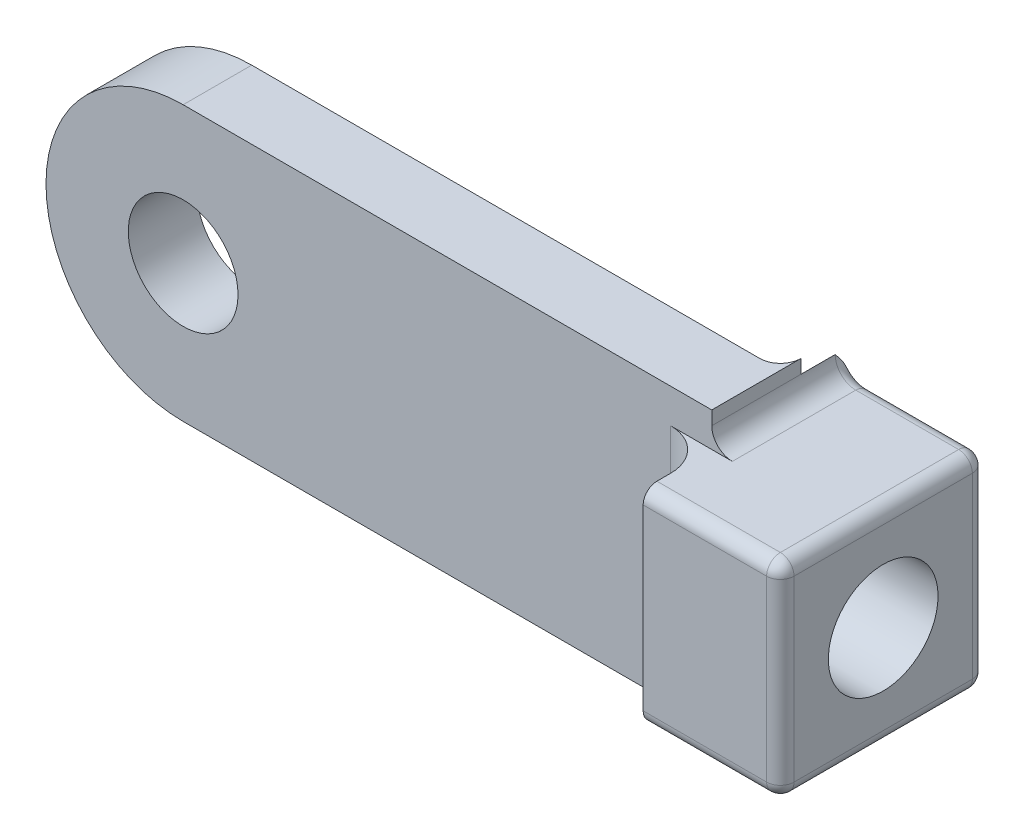
SolidWorks part; units mm, degrees
ref_plane "Front Plane" through (0, 0, 0) normal (0, 0, 1) x (1, 0, 0)
ref_plane "Top Plane" through (0, 0, 0) normal (0, 1, 0) x (1, 0, 0)
ref_plane "Right Plane" through (0, 0, 0) normal (1, 0, 0) x (0, 0, -1)
sketch "Sketch1" plane through (0, 0, 0) normal (0, 0, 1) x (1, 0, 0)
  line L0 (-22.5, 0) -> (22.5, 0) construction
  line L1 (-22.5, 10) -> (22.5, 10)
  line L2 (-22.5, -10) -> (22.5, -10)
  arc A0 (-22.5, 10) -> (-22.5, -10) centre (-22.5, 0) ccw
  arc A1 (22.5, -10) -> (22.5, 10) centre (22.5, 0) ccw
  circle A2 centre (-22.5, 0) radius 4
  circle A3 centre (22.5, 0) radius 4
  point P2 (0, 0)
  dimension "D3" = 8
  dimension "D4" = 8
  dimension "D1" = 20
  dimension "D2" = 45
extrude "Boss-Extrude1" add sketch "Sketch1" along normal blind 5
sketch "Sketch2" plane through (0, 0, 5) normal (0, 0, 1) x (1, 0, 0)
  line L0 (22.5, 10) -> (-22.5, 10) construction
  line L1 (16.0416, 10) -> (41.2048, 10)
  line L2 (16.0416, 10) -> (16.0416, -10)
  line L3 (16.0416, -10) -> (41.2048, -10)
  line L4 (41.2048, 10) -> (41.2048, -10)
  line L5 (-22.5, -10) -> (22.5, -10) construction
extrude "Cut-Extrude1" cut sketch "Sketch2" against normal through all
sketch "Sketch3" plane through (16.0416, 0, 0) normal (1, 0, 0) x (0, 0, -1)
  line L1 (5, -7.5) -> (-10, -7.5)
  line L2 (5, -7.5) -> (5, 7.5)
  line L3 (5, 7.5) -> (-10, 7.5)
  line L4 (-10, -7.5) -> (-10, 7.5)
  line L6 (0, 10) -> (-5, 10) construction
  line L7 (-5, 10) -> (-5, -10) construction
  line L8 (0, 10) -> (0, -10) construction
  point P6 (5, 0)
  dimension "D1" = 10
  dimension "D2" = 5
  dimension "D3" = 5
  dimension "D4" = 15
extrude "Boss-Extrude2" add sketch "Sketch3" along normal blind 10
fillet "Fillet1" radius 1.5 3 edges at (16.0416, 7.5, 2.5) (16.0416, -7.5, 2.5) (16.0416, 0, 0)
fillet "Fillet2" radius 3 1 edges at (16.0416, 0, 5)
sketch "Sketch4" plane through (26.0416, 0, 0) normal (1, 0, 0) x (0, 0, -1)
  line L0 (-10, -7.5) -> (5, -7.5) construction
  line L1 (-10, 7.5) -> (-10, -7.5) construction
  circle A0 centre (-2.5, 0) radius 4
  point P2 (0, 0)
  point P5 (-2.5, -7.5)
  point P8 (-10, 0)
  dimension "D1" = 8
extrude "Cut-Extrude2" cut sketch "Sketch4" against normal blind 8
fillet "Fillet3" radius 1 6 edges at (16.4809, -7.9393, -5) (16.4809, 7.9393, -5) (21.7916, -7.5, -5) (21.0416, -7.5, 10) (21.0416, 7.5, 10) (21.7916, 7.5, -5)
fillet "Fillet4" radius 1 8 edges at (26.0416, 7.2071, -4.7071) (26.0416, 0, -5) (26.0416, -7.2071, -4.7071) (26.0416, -7.5, 2.5) (26.0416, -7.2071, 9.7071) (26.0416, 0, 10) (26.0416, 7.2071, 9.7071) (26.0416, 7.5, 2.5)
